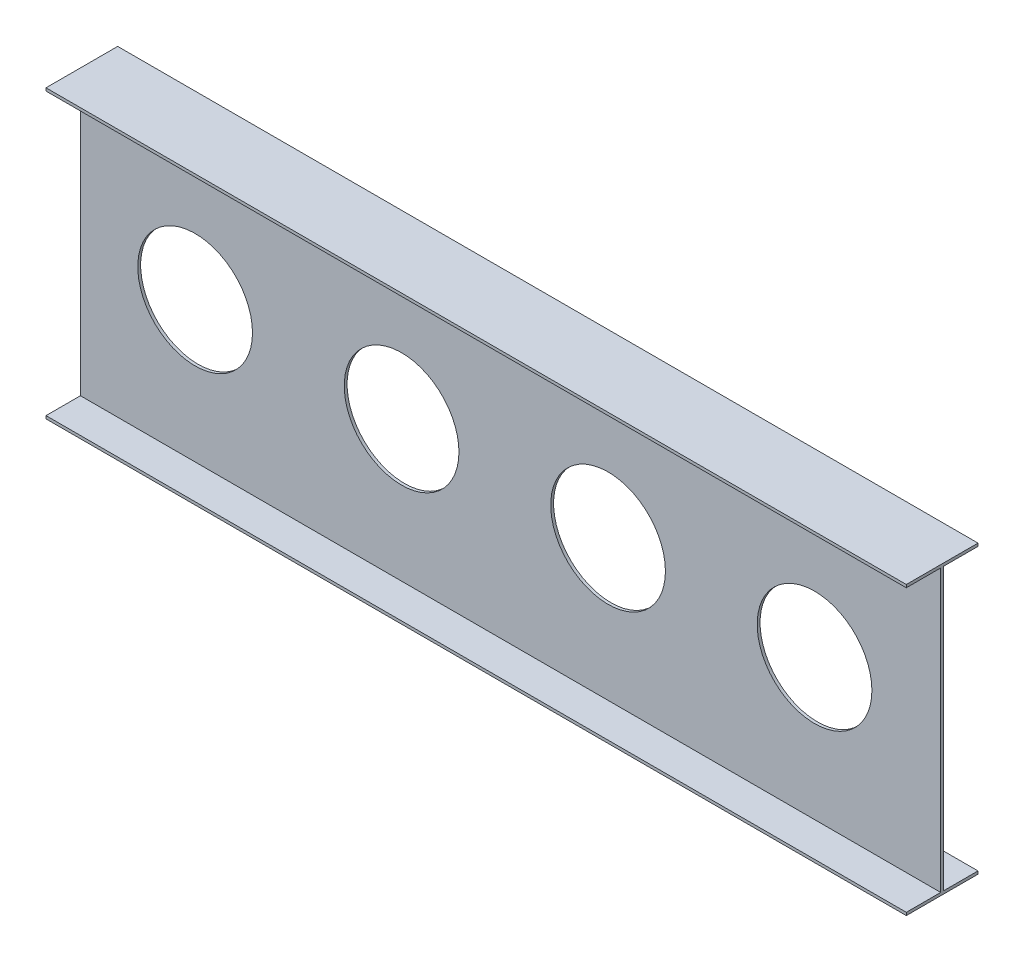
SolidWorks part; units mm, degrees
ref_plane "Front Plane" through (0, 0, 0) normal (0, 0, 1) x (1, 0, 0)
ref_plane "Top Plane" through (0, 0, 0) normal (0, 1, 0) x (1, 0, 0)
ref_plane "Right Plane" through (0, 0, 0) normal (1, 0, 0) x (0, 0, -1)
sketch "Sketch1" plane through (0, 0, 0) normal (1, 0, 0) x (0, 0, -1)
  line L0 (-4.5843, -956.1163) -> (115.4157, -956.1163)
  line L1 (-134.5843, 33.8837) -> (115.4157, 33.8837)
  line L2 (-134.5843, 33.8837) -> (-134.5843, 23.8837)
  line L3 (-134.5843, 23.8837) -> (-14.5843, 23.8837)
  line L4 (115.4157, 33.8837) -> (115.4157, 23.8837)
  line L5 (-134.5843, -956.1163) -> (-14.5843, -956.1163)
  line L6 (-134.5843, -956.1163) -> (-134.5843, -966.1163)
  line L7 (-134.5843, -966.1163) -> (115.4157, -966.1163)
  line L8 (115.4157, -956.1163) -> (115.4157, -966.1163)
  line L10 (-14.5843, 23.8837) -> (-14.5843, -956.1163)
  line L12 (-4.5843, 23.8837) -> (-4.5843, -956.1163)
  line L13 (-4.5843, 23.8837) -> (115.4157, 23.8837)
  line L14 (-14.5843, 23.8837) -> (-4.5843, 23.8837) construction
  dimension "D1" = 250
  dimension "D2" = 10
  dimension "D3" = 1000
extrude "Boss-Extrude1" add sketch "Sketch1" along normal blind 3000
sketch "Sketch2" plane through (0, 0, 14.5843) normal (0, 0, 1) x (1, 0, 0)
  line L2 (400, -466.1163) -> (1062.3009, -466.1163) construction
  line L3 (3000, 33.8837) -> (0, 33.8837) construction
  line L4 (3000, -966.1163) -> (0, -966.1163) construction
  line L5 (0, 23.8837) -> (0, -956.1163) construction
  circle A0 centre (400, -466.1163) radius 200
  circle A1 centre (1120, -466.1163) radius 200
  circle A2 centre (1840, -466.1163) radius 200
  circle A3 centre (2560, -466.1163) radius 200
  dimension "D3" = 400
  dimension "D1" = 400
  dimension "D2" = 4
extrude "Cut-Extrude1" cut sketch "Sketch2" against normal through all
